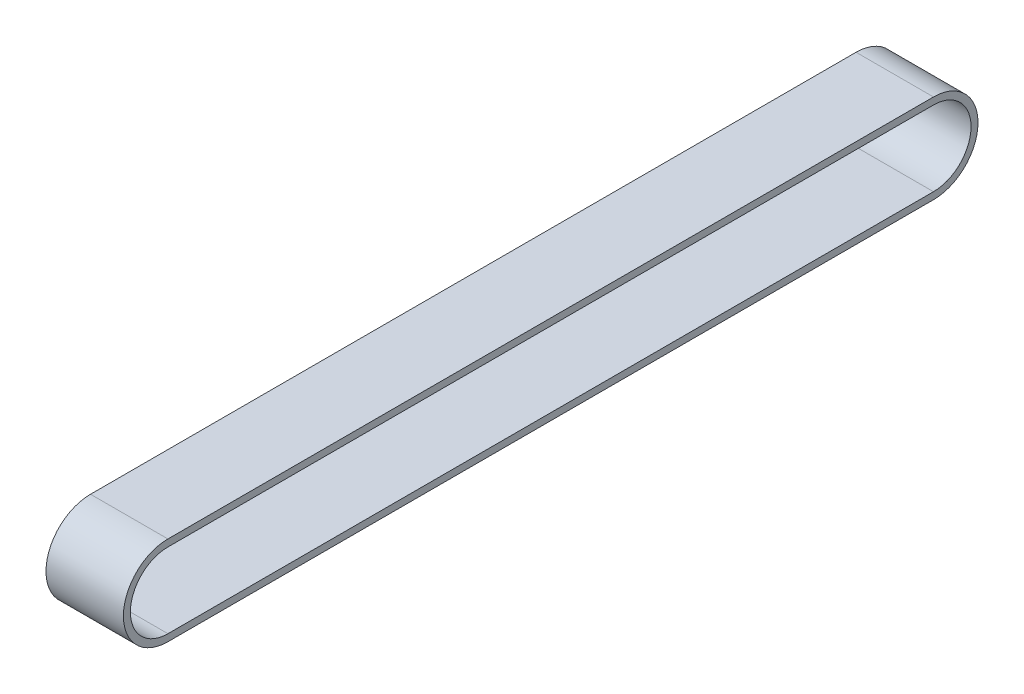
SolidWorks part; units mm, degrees
material "PUR"
ref_plane "Front" through (0, 0, 0) normal (0, 0, 1) x (1, 0, 0)
ref_plane "Top" through (0, 0, 0) normal (0, 1, 0) x (1, 0, 0)
ref_plane "Right" through (0, 0, 0) normal (1, 0, 0) x (0, 0, -1)
sketch "Sketch1" plane through (0, 0, 0) normal (1, 0, 0) x (0, 0, -1)
  line L0 (-125.5824, 0) -> (125.5824, 0) construction
  line L1 (-125.5824, 14.605) -> (125.5824, 14.605)
  line L2 (-125.5824, -14.605) -> (125.5824, -14.605)
  line L3 (-125.5824, 0) -> (125.5824, 0) construction
  line L4 (-125.5824, 12.319) -> (125.5824, 12.319)
  line L5 (-125.5824, -12.319) -> (125.5824, -12.319)
  arc A0 (-125.5824, 14.605) -> (-125.5824, -14.605) centre (-125.5824, 0) ccw
  arc A1 (125.5824, -14.605) -> (125.5824, 14.605) centre (125.5824, 0) ccw
  arc A2 (-125.5824, 12.319) -> (-125.5824, -12.319) centre (-125.5824, 0) ccw
  arc A3 (125.5824, -12.319) -> (125.5824, 12.319) centre (125.5824, 0) ccw
  point P2 (0, 0)
  point P9 (0, 0)
  point P16 (0, 0)
  dimension "D2" = 24.638
  dimension "D1" = 2.286
  dimension "D3" = 251.1648
extrude "Boss-Extrude1" add sketch "Sketch1" along normal mid plane 25.4
